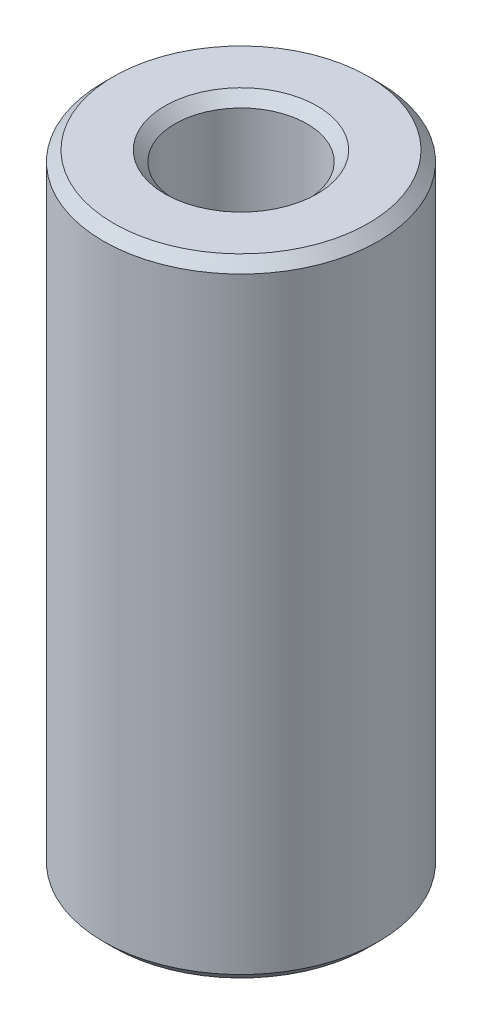
SolidWorks part; units mm, degrees
ref_plane "Front Plane" through (0, 0, 0) normal (0, 0, 1) x (1, 0, 0)
ref_plane "Top Plane" through (0, 0, 0) normal (0, 1, 0) x (1, 0, 0)
ref_plane "Right Plane" through (0, 0, 0) normal (1, 0, 0) x (0, 0, -1)
sketch "Sketch1" plane through (0, 0, 0) normal (0, 1, 0) x (1, 0, 0)
  circle A0 centre (0, 0) radius 30
  dimension "SLEEVE_OD" = 60
extrude "Boss-Extrude1" add sketch "Sketch1" along normal blind 136.7583
sketch "Sketch2" plane through (0, 0, 0) normal (0, 1, 0) x (1, 0, 0)
  circle A0 centre (0, 0) radius 14.3764
  dimension "BORE_D" = 28.7527
extrude "Cut-Extrude1" cut sketch "Sketch2" along normal through all
chamfer "Chamfer1" distance 2.2385 angle 45 4 edges at (0, 136.7583, 14.3764) (0, 0, 14.3764) (0, 0, 30) (0, 136.7583, 30)
